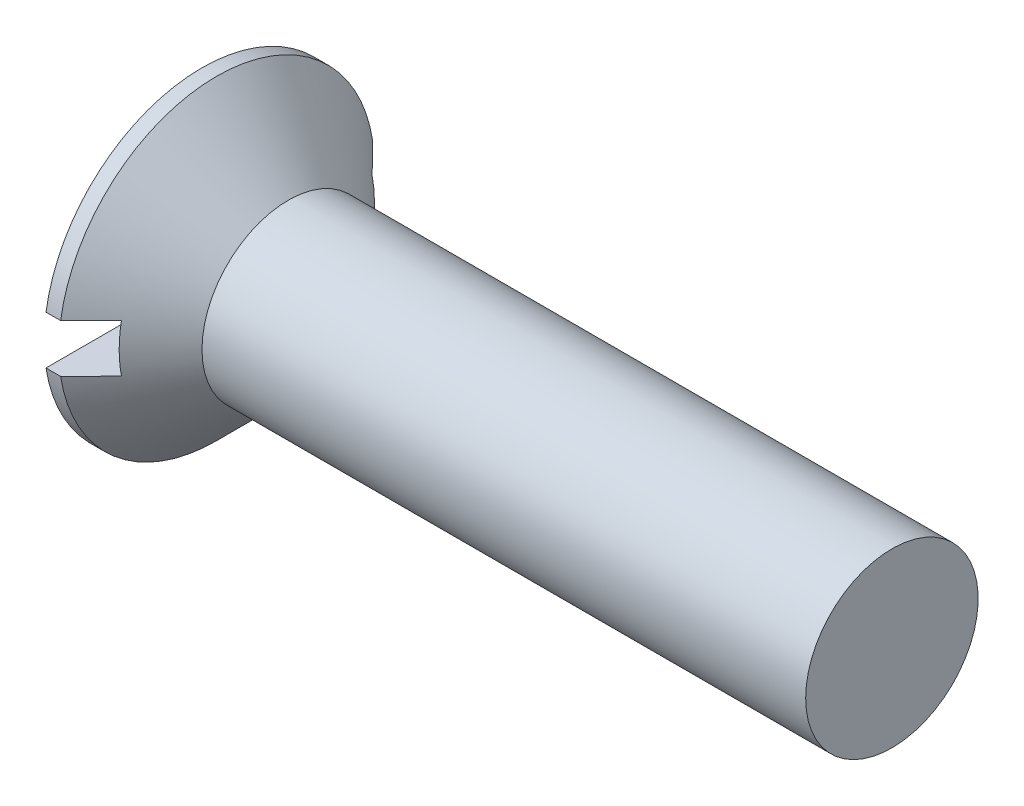
SolidWorks part; units mm, degrees
revolve "Base-Revolve" add sketch "BodySke" angle 360 about L5
sketch "BodySke" plane through (0, 0, 0) normal (0, 0, 1) x (1, 0, 0)
  line L0 (0, 0) -> (0, 9.15)
  line L1 (0, 9.15) -> (0.85, 9.15)
  line L2 (5, 5) -> (40, 5)
  line L3 (40, 5) -> (40, 0)
  line L4 (40, 0) -> (0, 0)
  line L5 (-6.35, 0) -> (82.55, 0) construction
  line L6 (5, -5) -> (40, -5) construction
  line L7 (0.85, -9.15) -> (5, -5) construction
  line L8 (0.85, 9.15) -> (5, 5)
  line L9 (0, -9.15) -> (0.85, -9.15) construction
  line L10 (6.5, 6.5875) -> (6.5, -2.9375) construction
  line L11 (5, 6.35) -> (5, -3.175) construction
  dimension "D6" = 0.85
  dimension "Diameter" = 10
cosmetic thread "ThreadCosmetic" [suppressed] parameters "Thread_length"=33.5, "Thread_minor"=8.344
extrude "Slot" cut sketch "Sketch2" against normal blind 2.6
sketch "Sketch2" plane through (0, 0, 0) normal (-1, 0, 0) x (0, 0, 1)
  line L0 (-9.15, -1.4) -> (9.15, -1.4)
  line L1 (-9.15, -1.4) -> (-9.15, 1.4)
  line L2 (9.15, 1.4) -> (-9.15, 1.4)
  line L3 (9.15, 1.4) -> (9.15, -1.4)
  dimension "D1" = 1.4
  dimension "D2" = 18.3
  dimension "D3" = 9.15
ref_plane "Plane1" through (0, 0, 0) normal (0, 0, 1) x (1, 0, 0)
ref_plane "Plane2" through (0, 0, 0) normal (0, 1, 0) x (1, 0, 0)
ref_plane "Plane3" through (0, 0, 0) normal (1, 0, 0) x (0, 0, -1)
sketch "Sketch3" plane through (0, 0, 0) normal (-1, 0, 0) x (0, 0, 1)
  line L0 (-0.99, 4.94) -> (0.99, 4.94)
  line L1 (0.99, 4.94) -> (0.99, -4.94)
  line L2 (0.99, -4.94) -> (-0.99, -4.94)
  line L3 (-0.99, -4.94) -> (-0.99, 4.94)
  dimension "Cross_dia" = 9.88
  dimension "Cross_width" = 1.98
  dimension "D1" = 4.94
  dimension "D2" = 0.99
ref_plane "Plane4" through (5.98, 0, 0) normal (-1, 0, 0) x (0, 0, 1)
sketch "Sketch4" plane through (5.98, 0, 0) normal (-1, 0, 0) x (0, 0, 1)
  line L0 (-0.495, 0.495) -> (0.495, 0.495)
  line L3 (0.495, 0.495) -> (0.495, -0.495)
  line L4 (0.495, -0.495) -> (-0.495, -0.495)
  line L5 (-0.495, -0.495) -> (-0.495, 0.495)
  dimension "D2" = 0.99
  dimension "D1" = 0.99
  dimension "D3" = 0.495
  dimension "D4" = 0.495
loft "Cross" cut profiles "Sketch3", "Sketch4"
pattern_circular "CirPattern1" count 2 every 90 about axis through (-6.35, 0, 0) along (1, 0, 0) of "Cross"
sketch "ThdSchSke" plane through (0, 0, 0) normal (0, 0, 1) x (1, 0, 0)
  line L0 (6.5, -4.172) -> (5.9202, -5)
  line L1 (6.5, -4.172) -> (7.0798, -5)
  line L2 (7.0798, -5) -> (7.0798, -6.25)
  line L3 (-3.175, 0) -> (5.1513, 0) construction
  line L5 (7.0798, -6.25) -> (5.9202, -6.25)
  line L6 (5.9202, -6.25) -> (5.9202, -5)
  line L7 (0, 9.15) -> (0, 1.4) construction
  dimension "Thread_minor" = 8.344
  dimension "Diameter" = 10
  dimension "Start" = 6.5
revolve "ThreadSchematic" [suppressed] cut sketch "ThdSchSke" angle 360 about L3
pattern_linear "ThdSchPat" [suppressed]
equation "\"D1@Sketch3\" = \"Cross_dia@Sketch3\" / 2"
equation "\"D2@Sketch3\" = \"Cross_width@Sketch3\" / 2"
equation "\"D1@Sketch4\" = \"Cross_width@Sketch3\" *.5"
equation "\"D2@Sketch4\" = \"D1@Sketch4\""
equation "\"D4@Sketch4\" = \"D2@Sketch4\" / 2"
equation "\"D3@Sketch4\" = \"D1@Sketch4\" / 2"
equation "\"D1@Sketch2\" = \"Slot_width@Sketch2\" / 2"
equation "\"D2@Sketch2\" = \"Head_dia@BodySke\""
equation "\"D3@Sketch2\" = \"D2@Sketch2\" / 2"
equation "\"Thread_length@ThreadCosmetic\" = ((sgn( (\"Length@BodySke\" - \"Advance@BodySke\" - \"Head_ht@BodySke\" ) - \"Thread_nom@BodySke\" )-1)*( (\"Length@BodySke\" - \"Advance@BodySke\" - \"Head_ht@BodySke\" ) - \"Thread_nom@BodySke\" ))/-2+ \"Thread_nom@BodySke\""
equation "\"Thread_minor@ThdSchSke\" = \"Thread_minor@ThreadCosmetic\""
equation "\"Diameter@ThdSchSke\" = \"Diameter@BodySke\""
equation "\"Overcut@ThdSchSke\" = \"Diameter@BodySke\" * 1.25"
equation "\"Start@ThdSchSke\" = 0.000001 + \"Length@BodySke\" - \"Thread_length@ThreadCosmetic\"  '---Countersunk---"
equation "\"Num_threads@ThdSchPat\" = int( \"Thread_length@ThreadCosmetic\" / \"Advance@BodySke\" + 0.999 )  + 1"
equation "\"Advance@ThdSchPat\" = \"Thread_length@ThreadCosmetic\" /  (\"Num_threads@ThdSchPat\" - 1) 'relax it"
